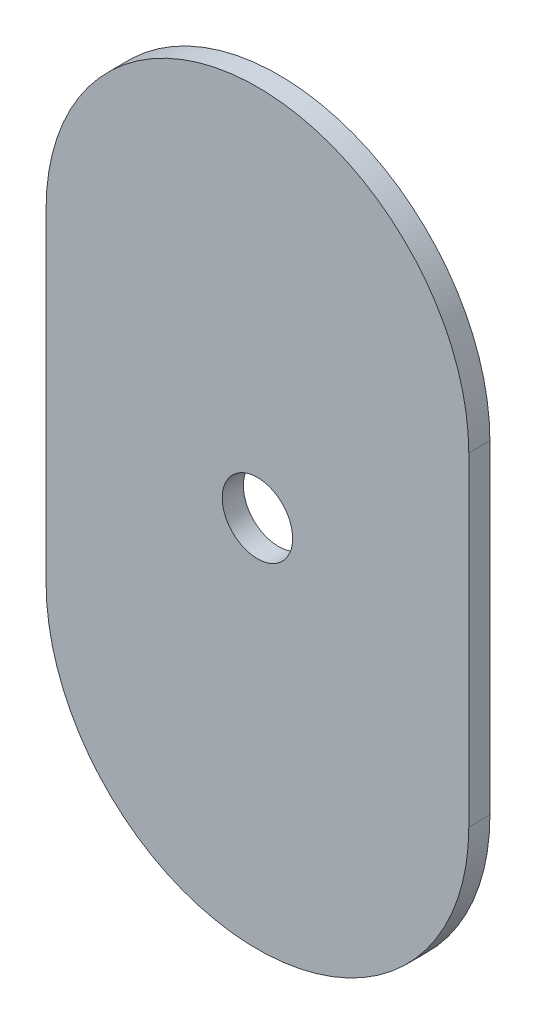
SolidWorks part; units mm, degrees
ref_plane "Płaszczyzna przednia" through (0, 0, 0) normal (0, 0, 1) x (1, 0, 0)
ref_plane "Płaszczyzna górna" through (0, 0, 0) normal (0, 1, 0) x (1, 0, 0)
ref_plane "Płaszczyzna prawa" through (0, 0, 0) normal (1, 0, 0) x (0, 0, -1)
sketch "Szkic33" plane through (0, 0, 0) normal (0, 0, 1) x (-1, 0, 0)
  line L0 (-44.5, 0) -> (45, 0) construction
  line L3 (0, 28.5) -> (0, -31.5) construction
  line L6 (-6, 12.5) -> (6, 12.5) construction
  line L9 (-6, 14.5) -> (6, 14.5)
  line L12 (-6, 10.5) -> (6, 10.5)
  line L13 (-6, -12.5) -> (6, -12.5) construction
  line L14 (-6, -14.5) -> (6, -14.5)
  line L15 (-6, -10.5) -> (6, -10.5)
  line L16 (-59.081, 0) -> (59.081, 0) construction
  circle A0 centre (0, 12.5) radius 4
  circle A4 centre (0, -12.5) radius 4
  arc A7 (-6, 14.5) -> (-6, 10.5) centre (-6, 12.5) ccw
  arc A8 (6, 10.5) -> (6, 14.5) centre (6, 12.5) ccw
  arc A9 (-6, -14.5) -> (-6, -10.5) centre (-6, -12.5) cw
  arc A10 (6, -10.5) -> (6, -14.5) centre (6, -12.5) cw
  point P14 (0, 12.5)
  point P26 (0, -12.5)
  point P34 (0, 0)
  dimension "D1" = 8
  dimension "D2" = 12.5
  dimension "D3" = 4
  dimension "D4" = 6
sketch "Szkic34" plane through (0, 0, 0) normal (0, 0, 1) x (1, 0, 0)
  line L12 (-47, 26.5) -> (-47, -26.5)
  line L13 (-43, -30.5) -> (43, -30.5)
  line L14 (47, -26.5) -> (47, 26.5)
  line L15 (43, 30.5) -> (-43, 30.5)
  spline S4 degree 3 poles (-43, 30.5) (-45.3431, 30.5) (-47, 28.8431) (-47, 26.5) knots 0 0 0 0 1 1 1 1 weights 1 0.804738 0.804738 1
  spline S5 degree 3 poles (-47, -26.5) (-47, -28.8431) (-45.3431, -30.5) (-43, -30.5) knots 0 0 0 0 1 1 1 1 weights 1 0.804738 0.804738 1
  spline S6 degree 3 poles (43, -30.5) (45.3431, -30.5) (47, -28.8431) (47, -26.5) knots 0 0 0 0 1 1 1 1 weights 1 0.804738 0.804738 1
  spline S7 degree 3 poles (47, 26.5) (47, 28.8431) (45.3431, 30.5) (43, 30.5) knots 0 0 0 0 1 1 1 1 weights 1 0.804738 0.804738 1
sketch "Szkic35" plane through (0, 0, 0) normal (0, 0, 1) x (1, 0, 0)
  line L0 (-15, -11.5) -> (-15, 11.5)
  line L1 (0, 16.5) -> (-15, 16.5) construction
  line L2 (0, 16.5) -> (15, 16.5) construction
  line L3 (22.2734, -16.5) -> (7.2734, -16.5) construction
  line L4 (22.2734, -16.5) -> (15, -16.5) construction
  line L5 (15, 11.5) -> (15, -11.5)
  line L8 (0, 26.5) -> (0, -26.5) construction
  line L9 (-15, 0) -> (15, 0) construction
  circle A0 centre (0, -12.5) radius 4 construction
  circle A1 centre (0, 12.5) radius 4 construction
  arc A2 (-15, 11.5) -> (15, 11.5) centre (0, 11.5) cw
  arc A3 (-15, -11.5) -> (15, -11.5) centre (0, -11.5) ccw
  circle A4 centre (0, 0) radius 2.5
  point P3 (0, 0)
  point P4 (0, 0)
  point P5 (0, 0)
  dimension "D6" = 1
  dimension "D7" = 1
  dimension "D8" = 5
  dimension "D1" = 15
  dimension "D2" = 15
  dimension "D3" = 5
  dimension "D4" = 5
  dimension "D5" = 15
  dimension "D9" = 15
extrude "Dodanie-wyciągnięcie2" add sketch "Szkic35" along normal blind 1.5
sketch "Szkic37" plane through (0, 0, 0) normal (0, 0, -1) x (-1, 0, 0)
  circle A0 centre (0, 12.5) radius 1.85
  circle A1 centre (0, -12.5) radius 1.85
  dimension "D1" = 3.7
  dimension "D2" = 2
extrude "Dodanie-wyciągnięcie3" add sketch "Szkic37" along normal blind 2
sketch "Szkic38" plane through (0, 0, -2) normal (0, 0, -1) x (-1, 0, 0)
  circle A0 centre (0, 12.5) radius 3.85
  circle A1 centre (0, -12.5) radius 3.85
  dimension "D1" = 7.7
  dimension "D2" = 2
extrude "Dodanie-wyciągnięcie4" add sketch "Szkic38" along normal blind 2
fillet "Zaokrąglenie1" radius 2 2 edges at (-3.85, -12.5, -4) (-3.85, 12.5, -4)
